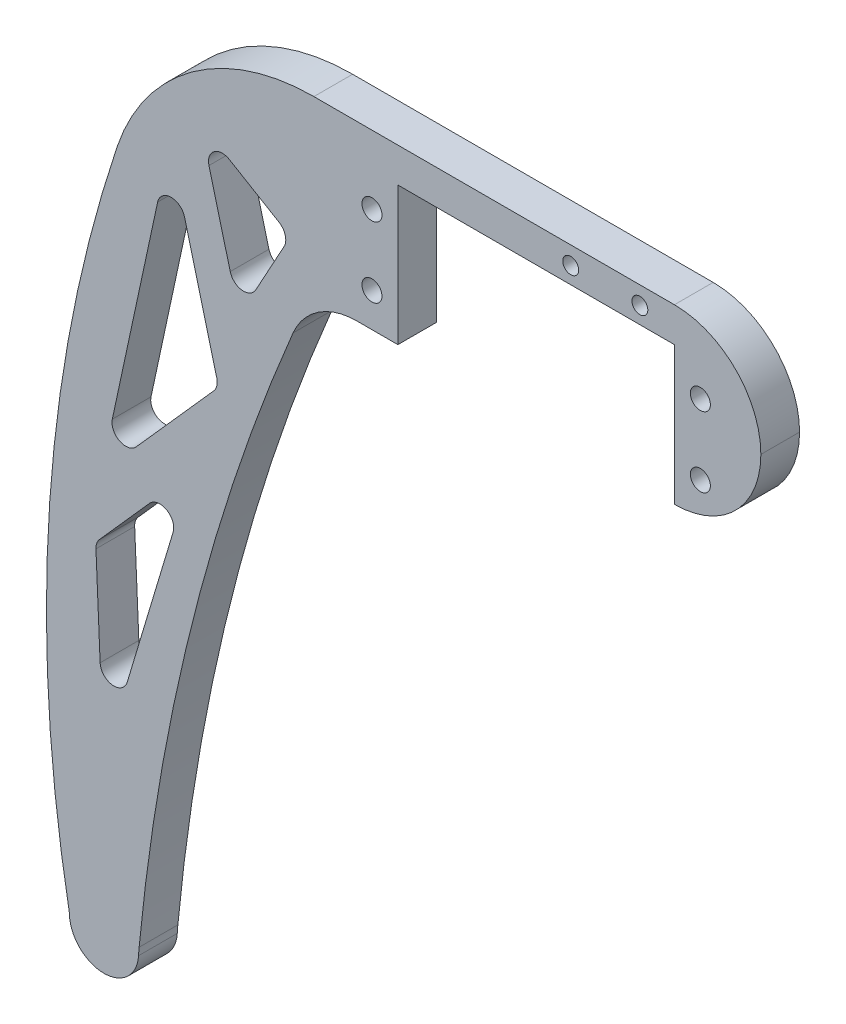
SolidWorks part; units mm, degrees
material "Acrylique (impact moyen-haut)"
ref_plane "Front" through (0, 0, 0) normal (0, 0, 1) x (1, 0, 0)
ref_plane "Top" through (0, 0, 0) normal (0, 1, 0) x (1, 0, 0)
ref_plane "Right" through (0, 0, 0) normal (1, 0, 0) x (0, 0, -1)
sketch "Esquisse1" plane through (0, 0, 0) normal (0, 0, 1) x (1, 0, 0)
  line L0 (-32.5, 12.5) -> (-52.5, 12.5)
  line L1 (-32.5, 12.5) -> (32.5, 12.5)
  line L3 (-32.5, -12.5) -> (32.5, -12.5)
  line L4 (32.5, 12.5) -> (32.5, -12.5)
  line L5 (-32.5, 12.5) -> (32.5, -12.5) construction
  line L6 (-32.5, -12.5) -> (32.5, 12.5) construction
  line L7 (-57.5, -107.5) -> (-67.5, -107.5) construction
  arc A3 (-32.5, -12.5) -> (-57.5, -107.5) centre (241.2075, -135.3178) ccw
  arc A4 (-57.5, -107.5) -> (-67.5, -107.5) centre (-62.5, -107.5) cw
  arc A5 (-52.5, 12.5) -> (-67.5, -107.5) centre (129.1682, -71.146) ccw
  point P0 (0, 0)
  point P12 (-62.5, -112.5)
  point P13 (-62.5, -107.5)
  dimension "D1" = 300
  dimension "D4" = 200
  dimension "D7" = 20
  dimension "D6" = 30
  dimension "D8" = 5
  dimension "D2" = 65
  dimension "D3" = 25
  dimension "D5" = 100
extrude "Boss.-Extru.1" add sketch "Esquisse1" along normal blind 5.6
sketch "Esquisse2" plane through (0, 0, 5.6) normal (0, 0, 1) x (1, 0, 0)
  line L0 (-32.5, 12.5) -> (-32.5, -12.5) construction
  line L1 (32.5, -12.5) -> (32.5, 12.5) construction
  line L2 (-32.5, -12.5) -> (32.5, -12.5) construction
  line L3 (-20, -12.5) -> (20, -12.5)
  line L4 (-20, -12.5) -> (-20, 7.5)
  line L5 (-20, 7.5) -> (20, 7.5)
  line L6 (20, -12.5) -> (20, 7.5)
  line L7 (-32.5, -12.5) -> (32.5, -12.5) construction
  dimension "D1" = 40
  dimension "D2" = 12.5
  dimension "D3" = 20
extrude "Enlèv. mat.-Extru.1" cut sketch "Esquisse2" against normal up to next
sketch "Esquisse3" plane through (0, 0, 5.6) normal (0, 0, 1) x (1, 0, 0)
  line L0 (-23.75, -7.58) -> (-20, -7.58) construction
  line L1 (-20, 7.5) -> (-20, -12.5) construction
  line L2 (23.75, -7.58) -> (20, -7.58) construction
  line L3 (20, -12.5) -> (20, 7.5) construction
  line L4 (-20, -2.5) -> (20, -2.5) construction
  circle A0 centre (-23.75, -7.58) radius 1.45
  circle A1 centre (23.75, -7.58) radius 1.45
  circle A2 centre (23.75, 2.58) radius 1.45
  circle A3 centre (-23.75, 2.58) radius 1.45
  dimension "D1" = 47.5
  dimension "D2" = 5.08
  dimension "D3" = 2.9
  dimension "D4" = 3.75
extrude "Enlèv. mat.-Extru.2" cut sketch "Esquisse3" against normal up to next
fillet "Congé2" radius 12.5 2 edges at (32.5, -12.5, 2.8) (32.5, 12.5, 2.8)
fillet "Congé3" radius 10 1 edges at (-32.5, -12.5, 2.8)
fillet "Congé4" radius 30 1 edges at (-52.5, 12.5, 2.8)
fillet "Congé5" radius 30 1 edges at (-57.5, -107.5, 2.8)
sketch "Esquisse4" plane through (0, 0, 5.6) normal (0, 0, 1) x (1, 0, 0)
  line L0 (-35.5305, -6.7417) -> (-42.9742, -20.3323)
  line L1 (-42.9742, -20.3323) -> (-48.5558, 0.9897)
  line L2 (-48.5558, 0.9897) -> (-35.5305, -6.7417)
  line L3 (-52.9829, -3.8169) -> (-45.9191, -30.8008)
  line L4 (-45.9191, -30.8008) -> (-62.9006, -49.9135)
  line L5 (-62.9006, -49.9135) -> (-52.9829, -3.8169)
  line L6 (-49.8982, -43.5599) -> (-63.7025, -59.0966)
  line L7 (-63.7025, -59.0966) -> (-62.553, -85.6965)
  line L8 (-62.553, -85.6965) -> (-49.8982, -43.5599)
  dimension "D1" = 5.5
  dimension "D2" = 5.5
extrude "Enlèv. mat.-Extru.3" cut sketch "Esquisse4" against normal up to next
fillet "Congé6" radius 2 9 edges at (-62.553, -85.6965, 2.8) (-63.7025, -59.0966, 2.8) (-49.8982, -43.5599, 2.8) (-45.9191, -30.8008, 2.8) (-52.9829, -3.8169, 2.8) (-62.9006, -49.9135, 2.8) (-42.9742, -20.3323, 2.8) (-35.5305, -6.7417, 2.8) (-48.5558, 0.9897, 2.8)
sketch "Esquisse5" plane through (0, 0, 5.6) normal (0, 0, 1) x (1, 0, 0)
  line L0 (20, 12.5) -> (-32.1455, 12.5) construction
  line L2 (20, -12.5) -> (20, 7.5) construction
  circle A0 centre (15, 9.91) radius 1.15
  circle A1 centre (5, 9.91) radius 1.15
  dimension "D1" = 2.59
  dimension "D2" = 10
  dimension "D3" = 5
  dimension "D4" = 2.3
extrude "Enlèv. mat.-Extru.4" cut sketch "Esquisse5" against normal up to next
